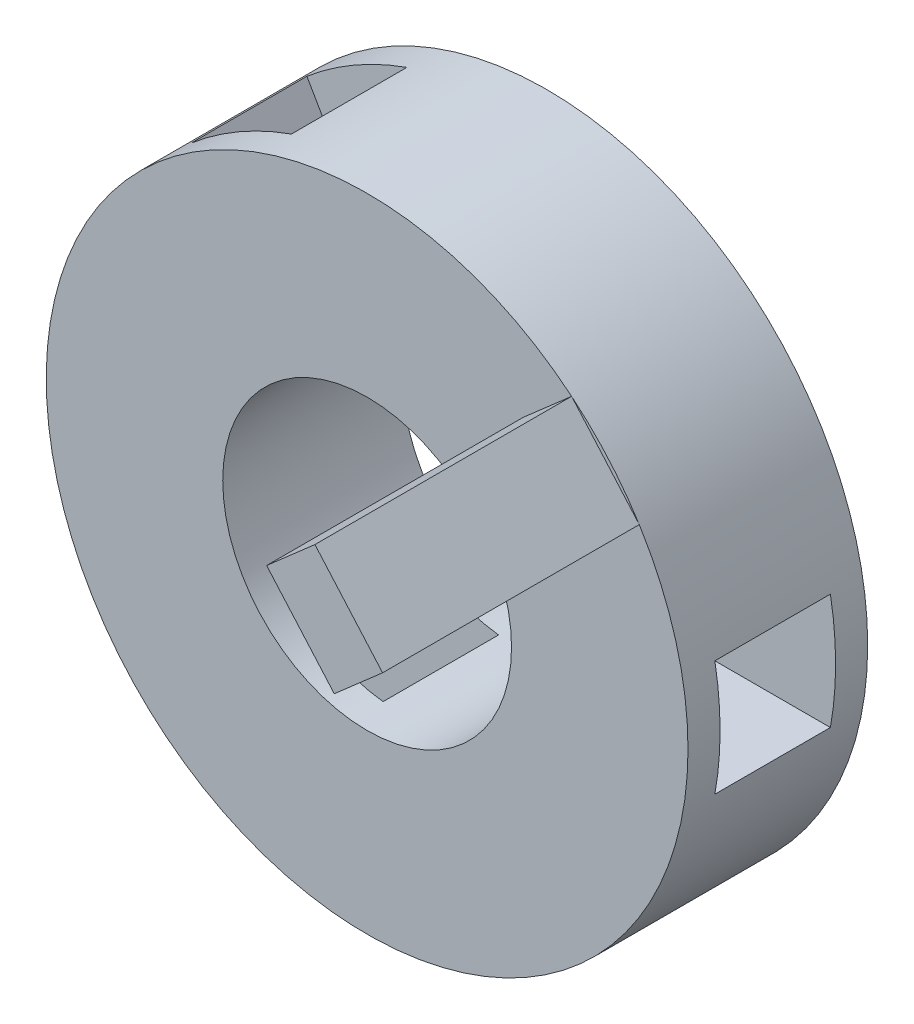
SolidWorks part; units mm, degrees
ref_plane "Plan de face" through (0, 0, 0) normal (0, 0, 1) x (1, 0, 0)
ref_plane "Plan de dessus" through (0, 0, 0) normal (0, 1, 0) x (1, 0, 0)
ref_plane "Plan de droite" through (0, 0, 0) normal (1, 0, 0) x (0, 0, -1)
sketch "Esquisse1" plane through (0, 0, 0) normal (0, 0, 1) x (1, 0, 0)
  circle A0 centre (0, 0) radius 25
  dimension "D1" = 50
extrude "Boss.-Extru.1" add sketch "Esquisse1" along normal blind 14 contours A0
sketch "Esquisse2" plane through (0, 0, 0) normal (1, 0, 0) x (0, 0, -1)
  line L0 (0, -25) -> (0, 25) construction
  line L1 (-11.5, 4.5) -> (-2.5, 4.5)
  line L2 (-11.5, 4.5) -> (-11.5, -4.5)
  line L3 (-11.5, -4.5) -> (-2.5, -4.5)
  line L4 (-2.5, 4.5) -> (-2.5, -4.5)
  dimension "D1" = 9
  dimension "D2" = 9
  dimension "D3" = 2.5
  dimension "D5" = 4.5
extrude "Enlèv. mat.-Extru.1" cut sketch "Esquisse2" against normal blind 16 from offset 26
pattern_circular "Répétition circulaire1" count 3 over 360 about axis through (0, 0, 14) along (0, 0, -1) of "Enlèv. mat.-Extru.1"
sketch "Esquisse9" plane through (0, 0, 0) normal (0, 0, -1) x (-1, 0, 0)
  circle A0 centre (0, 0) radius 11.25
  dimension "D1" = 22.5
extrude "Enlèv. mat.-Extru.2" cut sketch "Esquisse9" against normal blind 16 contours A0
sketch "Esquisse10" plane through (0, 0, 0) normal (0, 0, -1) x (-1, 0, 0)
  line L0 (-15.9324, 19.2654) -> (-21.2022, 13.2464)
  line L1 (-21.2022, 13.2464) -> (-17.4403, 9.9527)
  line L2 (-17.4403, 9.9527) -> (-12.1705, 15.9718)
  line L3 (-12.1705, 15.9718) -> (-15.9324, 19.2654)
  circle A1 centre (0, 0) radius 25 construction
  dimension "D1" = 8
  dimension "D2" = 5
extrude "Boss.-Extru.3" add sketch "Esquisse10" against normal blind 20 from surface contours L1 L2 L3 L0 starting at face at (11.25, 0, 14)
